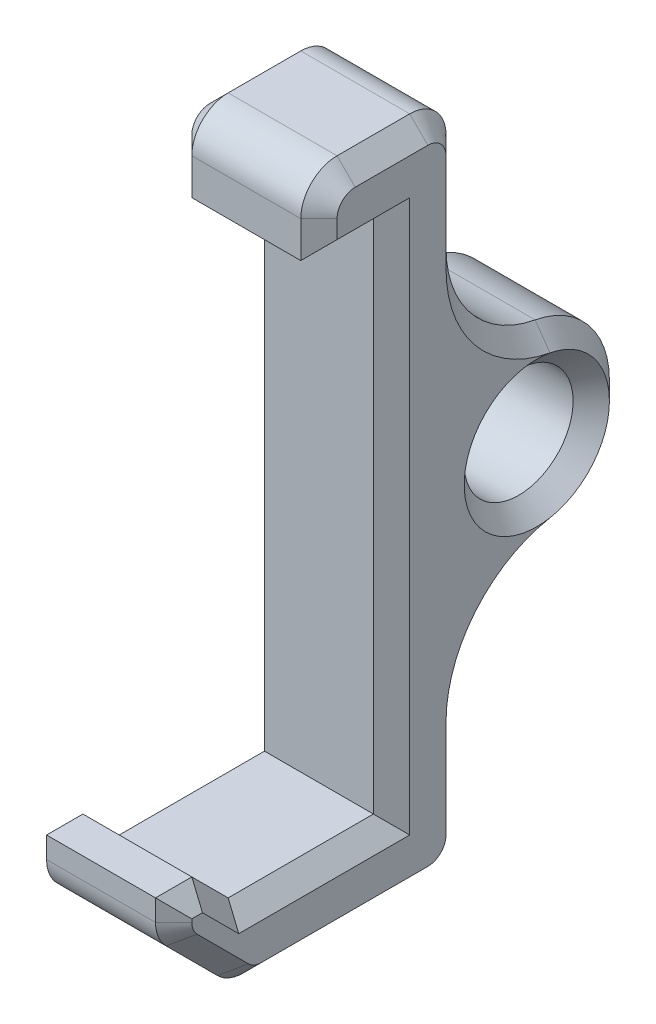
SolidWorks part; units mm, degrees
ref_plane "Front Plane" through (0, 0, 0) normal (0, 0, 1) x (1, 0, 0)
ref_plane "Top Plane" through (0, 0, 0) normal (0, 1, 0) x (1, 0, 0)
ref_plane "Right Plane" through (0, 0, 0) normal (1, 0, 0) x (0, 0, -1)
sketch "Sketch2" plane through (0, 0, 0) normal (1, 0, 0) x (0, 0, -1)
  line L0 (0, 7.1) -> (0, -7.1)
  line L1 (0, -7.1) -> (-4, -7.1)
  line L2 (-4, -7.1) -> (-5, -6.1)
  line L3 (-5, -6.1) -> (-6, -6.1)
  line L4 (-6, -6.1) -> (-6, -7.1)
  line L5 (-6, -7.1) -> (-4, -9.1)
  line L6 (-4, -9.1) -> (2, -9.1)
  line L7 (2, -9.1) -> (2, -2.5)
  line L8 (2, -2.5) -> (4, -2.5)
  line L9 (4, 2.5) -> (2, 2.5)
  line L10 (2, 2.5) -> (2, 9.1)
  line L11 (2, 9.1) -> (-2, 9.1)
  line L12 (-2, 9.1) -> (-2, 7.1)
  line L13 (-2, 7.1) -> (0, 7.1)
  arc A0 (4, 2.5) -> (4, -2.5) centre (4, 0) cw
  circle A1 centre (4, 0) radius 1.5
  point P17 (-6.4182, -7.4689)
  point P18 (0, 0)
  point P19 (-6, -7.5421)
  dimension "D10" = 3
  dimension "D1" = 14.2
  dimension "D2" = 2
  dimension "D3" = 2
  dimension "D4" = 4
  dimension "D5" = 1
  dimension "D6" = 2
  dimension "D7" = 5
  dimension "D8" = 2
  dimension "D9" = 2
  dimension "D11" = 1
  dimension "D12" = 135
extrude "Boss-Extrude1" add sketch "Sketch2" along normal blind 2 and the other way blind 2 contours A0 L9 L10 L11 L12 L13 L0 L1 L2 L3 L4 L5 L6 L7 L8 A1 region at (0, -0.8959, -0.7834)
fillet "Fillet1" radius 3 2 edges at (0, 2.5, -2) (0, -2.5, -2)
fillet "Fillet2" radius 1 5 edges at (0, 9.1, 2) (0, -7.1, 6) (0, -9.1, 4) (0, -9.1, -2) (0, 9.1, -2)
chamfer "Chamfer1" distance 0.5 angle 45 42 edges at (-2, 7.1, 1) (-2, 0, 0) (-2, -7.1, 2) (-2, -6.6, 4.5) (-2, -6.1, 5.5) (-2, -6.3929, 6) (-2, -7.0685, 5.9239) (-2, -8.1, 5) (-2, -9.0239, 3.9685) (-2, -9.1, 1.2929) (-2, -8.8071, -1.7071) (-2, -6.7542, -2) (-2, -3.4895, -2.6939) (-2, 0, -6.5) (-2, 3.4895, -2.6939) (-2, 6.7542, -2) (-2, 8.8071, -1.7071) (-2, 9.1, 0) (-2, 8.8071, 1.7071) (-2, 7.6, 2) (-2, 0, -5.5) (2, 8.8071, -1.7071) (2, 6.7542, -2) (2, 3.4895, -2.6939) (2, 0, -6.5) (2, -3.4895, -2.6939) (2, -6.7542, -2) (2, -8.8071, -1.7071) (2, -9.1, 1.2929) (2, -9.0239, 3.9685) (2, -8.1, 5) (2, -7.0685, 5.9239) (2, -6.3929, 6) (2, -6.1, 5.5) (2, -6.6, 4.5) (2, -7.1, 2) (2, 0, 0) (2, 7.1, 1) (2, 7.6, 2) (2, 8.8071, 1.7071) (2, 9.1, 0) (2, 0, -5.5)
